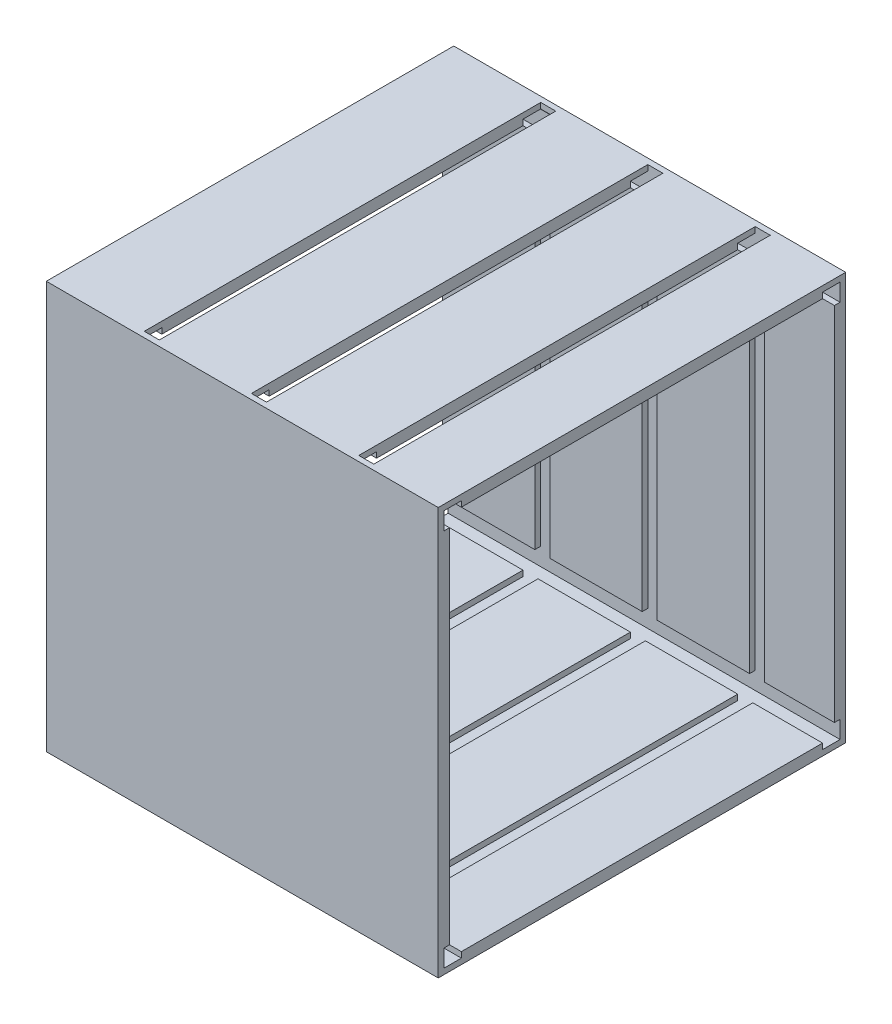
SolidWorks part; units mm, degrees
ref_plane "Front Plane" through (0, 0, 0) normal (0, 0, 1) x (1, 0, 0)
ref_plane "Top Plane" through (0, 0, 0) normal (0, 1, 0) x (1, 0, 0)
ref_plane "Right Plane" through (0, 0, 0) normal (1, 0, 0) x (0, 0, -1)
sketch "Sketch1" plane through (0, 0, 0) normal (1, 0, 0) x (0, 0, -1)
  line L1 (0, 0) -> (688.1, 0)
  line L2 (0, 0) -> (0, 688.1)
  line L3 (0, 688.1) -> (688.1, 688.1)
  line L4 (688.1, 0) -> (688.1, 688.1)
  line L5 (0, 0) -> (19.05, 0) construction
  line L6 (0, 0) -> (0, 19.05) construction
  line L7 (0, 19.05) -> (19.05, 19.05) construction
  line L8 (19.05, 0) -> (19.05, 19.05) construction
  line L9 (19.05, 19.05) -> (669.05, 19.05)
  line L10 (19.05, 19.05) -> (19.05, 669.05)
  line L11 (19.05, 669.05) -> (669.05, 669.05)
  line L12 (669.05, 19.05) -> (669.05, 669.05)
  dimension "D1" = 688.1
  dimension "D2" = 688.1
  dimension "D3" = 19.05
  dimension "D4" = 19.05
  dimension "D5" = 650
  dimension "D6" = 650
extrude "Boss-Extrude1" add sketch "Sketch1" along normal blind 661.9 contours L10 L11 L12 L9 | L2 L3 L4 L1
sketch "Sketch3" plane through (0, 0, -669.05) normal (0, 0, 1) x (1, 0, 0)
  line L1 (0, 669.05) -> (155.95, 669.05) construction
  line L2 (0, 669.05) -> (0, 19.05) construction
  line L3 (0, 19.05) -> (155.95, 19.05) construction
  line L4 (155.95, 669.05) -> (155.95, 19.05) construction
  line L5 (155.95, 669.05) -> (181.35, 669.05)
  line L6 (155.95, 669.05) -> (155.95, 19.05)
  line L7 (155.95, 19.05) -> (181.35, 19.05)
  line L8 (181.35, 669.05) -> (181.35, 19.05)
  line L9 (337.3, 669.05) -> (362.7, 669.05)
  line L10 (337.3, 669.05) -> (337.3, 19.05)
  line L11 (337.3, 19.05) -> (362.7, 19.05)
  line L12 (362.7, 669.05) -> (362.7, 19.05)
  line L13 (518.65, 669.05) -> (544.05, 669.05)
  line L14 (518.65, 669.05) -> (518.65, 19.05)
  line L15 (518.65, 19.05) -> (544.05, 19.05)
  line L16 (544.05, 669.05) -> (544.05, 19.05)
  line L17 (661.9, 688.1) -> (0, 688.1) construction
  point P15 (350, 669.05)
  dimension "D1" = 155.95
  dimension "D2" = 650
  dimension "D3" = 25.4
  dimension "D4" = 25.4
  dimension "D5" = 650
  dimension "D6" = 155.95
  dimension "D7" = 25.4
  dimension "D8" = 650
  dimension "D9" = 155.95
  dimension "D10" = 19.05
  dimension "D11" = 19.05
extrude "Cut-Extrude1" cut sketch "Sketch3" against normal blind 9.525
ref_plane "Plane1" through (0, 0, -344.05) normal (0, 0, -1) x (-1, 0, 0)
mirror "Mirror2" about plane through (0, 0, -344.05) normal (0, 0, -1) of "Cut-Extrude1"
ref_plane "Plane2" through (0, 344.05, 0) normal (0, 1, 0) x (1, 0, 0)
sketch "Sketch4" plane through (0, 19.05, 0) normal (0, 1, 0) x (1, 0, 0)
  line L0 (661.9, 688.1) -> (0, 688.1) construction
  line L1 (155.95, 678.575) -> (181.35, 678.575)
  line L2 (155.95, 678.575) -> (155.95, 9.075)
  line L3 (155.95, 9.075) -> (181.35, 9.075)
  line L4 (181.35, 678.575) -> (181.35, 9.075)
  line L5 (0, 0) -> (0, 688.1) construction
  line L6 (661.9, 0) -> (0, 0) construction
  line L7 (337.3, 678.575) -> (362.7, 678.575)
  line L8 (337.3, 678.575) -> (337.3, 9.075)
  line L9 (337.3, 9.075) -> (362.7, 9.075)
  line L10 (362.7, 678.575) -> (362.7, 9.075)
  line L11 (518.65, 678.575) -> (544.05, 678.575)
  line L12 (518.65, 678.575) -> (518.65, 9.525)
  line L13 (518.65, 9.525) -> (544.05, 9.525)
  line L14 (544.05, 678.575) -> (544.05, 9.525)
  dimension "D1" = 25.4
  dimension "D2" = 669.5
  dimension "D3" = 9.525
  dimension "D4" = 155.95
  dimension "D5" = 669.5
  dimension "D6" = 25.4
  dimension "D7" = 9.525
  dimension "D8" = 155.95
  dimension "D9" = 25.4
  dimension "D10" = 155.95
  dimension "D11" = 9.525
  dimension "D12" = 9.525
extrude "Cut-Extrude3" cut sketch "Sketch4" against normal blind 9.525
mirror "Mirror4" about plane through (0, 344.05, 0) normal (0, 1, 0) of "Cut-Extrude3"
sketch "Sketch6" plane through (0, 688.1, 0) normal (0, 1, 0) x (1, 0, 0)
  line L0 (0, 0) -> (0, 688.1) construction
  line L1 (155.95, 679.025) -> (181.35, 679.025)
  line L2 (155.95, 679.025) -> (155.95, 9.525)
  line L3 (155.95, 9.525) -> (181.35, 9.525)
  line L4 (181.35, 679.025) -> (181.35, 9.525)
  line L5 (337.3, 678.575) -> (362.7, 678.575)
  line L6 (337.3, 678.575) -> (337.3, 9.075)
  line L7 (337.3, 9.075) -> (362.7, 9.075)
  line L8 (362.7, 678.575) -> (362.7, 9.075)
  line L9 (518.65, 678.575) -> (544.05, 678.575)
  line L10 (518.65, 678.575) -> (518.65, 9.075)
  line L11 (518.65, 9.075) -> (544.05, 9.075)
  line L12 (544.05, 678.575) -> (544.05, 9.075)
  line L13 (661.9, 0) -> (0, 0) construction
  line L14 (661.9, 688.1) -> (0, 688.1) construction
  dimension "D1" = 669.5
  dimension "D2" = 25.4
  dimension "D3" = 155.95
  dimension "D4" = 9.525
  dimension "D5" = 25.4
  dimension "D6" = 669.5
  dimension "D7" = 9.525
  dimension "D8" = 155.95
  dimension "D9" = 25.4
  dimension "D10" = 669.5
  dimension "D11" = 9.525
  dimension "D12" = 155.95
extrude "Cut-Extrude4" cut sketch "Sketch6" against normal blind 9.525
sketch "Sketch7" plane through (0, 0, 0) normal (-1, 0, 0) x (0, 0, 1)
  line L0 (-19.05, 39.05) -> (-9.525, 39.05)
  line L1 (-19.05, 19.05) -> (-19.05, 669.05) construction
  line L2 (-9.525, 39.05) -> (-9.525, 9.525)
  line L3 (-9.525, 9.525) -> (-39.05, 9.525)
  line L4 (-39.05, 9.525) -> (-39.05, 19.05)
  line L5 (-19.05, 19.05) -> (-669.05, 19.05) construction
  line L6 (-39.05, 19.05) -> (-19.05, 19.05)
  line L7 (-19.05, 19.05) -> (-19.05, 39.05)
  dimension "D1" = 9.525
  dimension "D2" = 20
  dimension "D3" = 20
  dimension "D4" = 9.525
extrude "Cut-Extrude5" cut sketch "Sketch7" against normal blind 700
mirror "Mirror5" about plane through (0, 0, -344.05) normal (0, 0, -1) of "Cut-Extrude5"
mirror "Mirror6" about plane through (0, 344.05, 0) normal (0, 1, 0) of "Mirror5"
